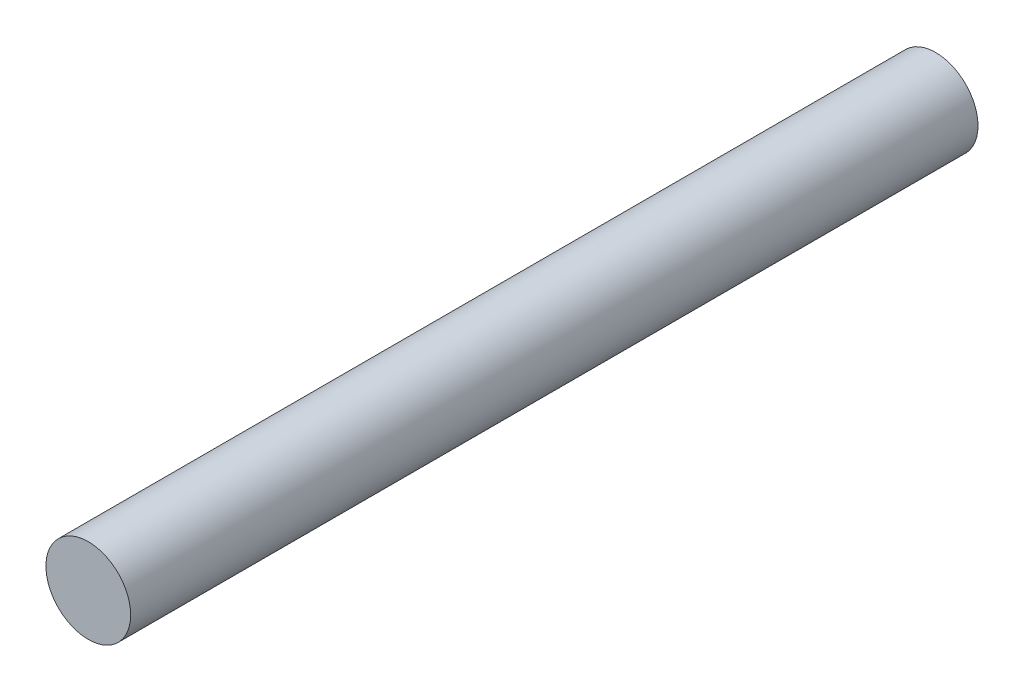
SolidWorks part; units mm, degrees
ref_plane "Front Plane" through (0, 0, 0) normal (0, 0, 1) x (1, 0, 0)
ref_plane "Top Plane" through (0, 0, 0) normal (0, 1, 0) x (1, 0, 0)
ref_plane "Right Plane" through (0, 0, 0) normal (1, 0, 0) x (0, 0, -1)
sketch "Sketch1" plane through (0, 0, 0) normal (0, 0, 1) x (1, 0, 0)
  circle A0 centre (-941.663, 304.3873) radius 1
  dimension "D1" = 2
extrude "Boss-Extrude1" add sketch "Sketch1" along normal blind 10 and the other way blind 10
